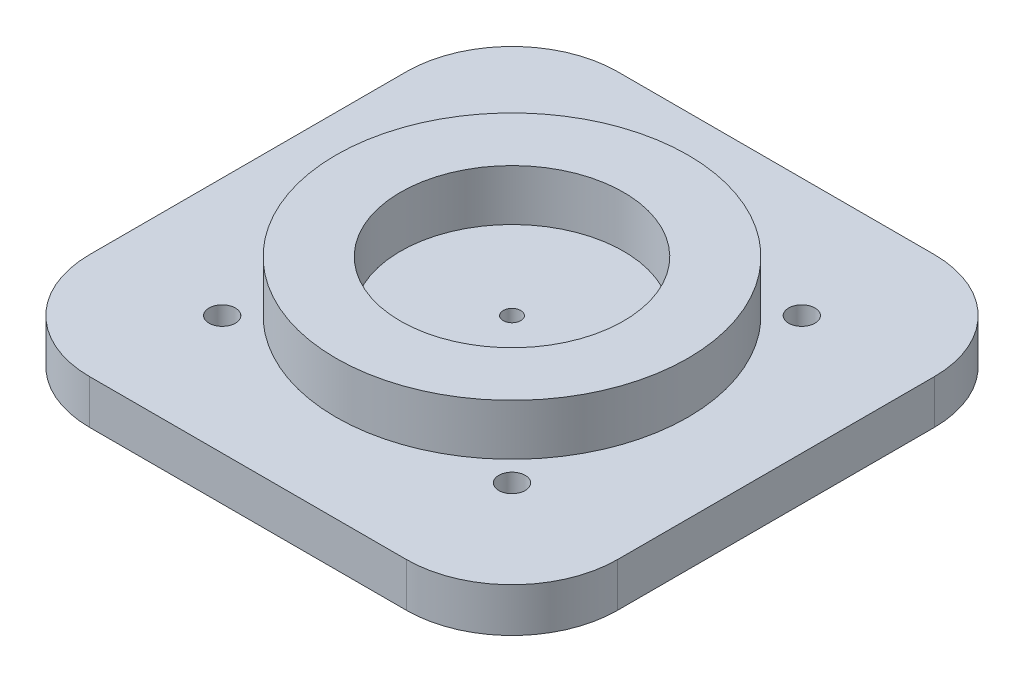
SolidWorks part; units mm, degrees
material "ABS PC"
ref_plane "Front Plane" through (0, 0, 0) normal (0, 0, 1) x (1, 0, 0)
ref_plane "Top Plane" through (0, 0, 0) normal (0, 1, 0) x (1, 0, 0)
ref_plane "Right Plane" through (0, 0, 0) normal (1, 0, 0) x (0, 0, -1)
sketch "Sketch1" plane through (0, 0, 0) normal (0, 1, 0) x (1, 0, 0)
  line L0 (0, 50.8) -> (4.4901, 46.3099)
  line L1 (0, 0) -> (50.8, 0)
  line L2 (0, 0) -> (0, 50.8)
  line L3 (0, 50.8) -> (50.8, 50.8)
  line L4 (50.8, 0) -> (50.8, 50.8)
  line L5 (0, 25.4) -> (50.8, 25.4) construction
  line L6 (25.4, 50.8) -> (25.4, 0) construction
  circle A0 centre (4.4901, 46.3099) radius 1.905
  circle A1 centre (4.4901, 4.4901) radius 1.905
  circle A2 centre (46.3099, 4.4901) radius 1.905
  circle A3 centre (46.3099, 46.3099) radius 1.905
  circle A28 centre (25.4, 25.4) radius 1.27
  dimension "D1" = 3.81
  dimension "D2" = 50.8
  dimension "D3" = 50.8
  dimension "D4" = 6.35
extrude "Boss-Extrude1" add sketch "Sketch1" along normal blind 6.35 contours A0 L2 L1 L4 L3 A1 A2 A3 region at (25.4, 0, -50.0816)
sketch "Sketch2" plane through (0, 0, 0) normal (0, 1, 0) x (1, 0, 0)
  line L0 (4.4901, 44.2975) -> (4.4901, 6.5025)
  line L1 (6.5025, 4.4901) -> (44.2975, 4.4901)
  line L2 (46.3099, 44.2975) -> (46.3099, 6.5025)
  line L3 (44.2975, 46.3099) -> (6.5025, 46.3099)
  circle A0 centre (4.4901, 46.3099) radius 1.905
  circle A1 centre (4.4901, 46.3099) radius 2.0124
  circle A2 centre (46.3099, 46.3099) radius 1.905
  circle A3 centre (46.3099, 46.3099) radius 2.0124
  circle A4 centre (46.3099, 4.4901) radius 1.905
  circle A5 centre (46.3099, 4.4901) radius 2.0124
  circle A6 centre (4.4901, 4.4901) radius 1.905
  circle A7 centre (4.4901, 4.4901) radius 2.0124
extrude "Cut-Extrude1" [suppressed] cut sketch "Sketch2" along normal blind 1.5875 from surface contours A7 L1 A5 L2 A3 L3 A1 L0 starting at face at (4.4901, 0, -44.4049)
sketch "Sketch3" plane through (0, 0, 0) normal (0, 1, 0) x (1, 0, 0)
  line L0 (3.2513, 44.2975) -> (3.2513, 6.5025)
  line L1 (6.5025, 3.2513) -> (44.2975, 3.2513)
  line L2 (47.5487, 44.2975) -> (47.5487, 6.5025)
  line L3 (44.2975, 47.5487) -> (6.5025, 47.5487)
  circle A0 centre (3.2513, 47.5487) radius 1.905
  circle A1 centre (3.2513, 47.5487) radius 3.2513
  circle A2 centre (47.5487, 47.5487) radius 1.905
  circle A3 centre (47.5487, 47.5487) radius 3.2513
  circle A4 centre (47.5487, 3.2513) radius 1.905
  circle A5 centre (47.5487, 3.2513) radius 3.2513
  circle A6 centre (3.2513, 3.2513) radius 1.905
  circle A7 centre (3.2513, 3.2513) radius 3.2513
extrude "Cut-Extrude2" [suppressed] cut sketch "Sketch3" against normal blind 1.5875 from surface contours A7 L1 A5 L2 A3 L3 A1 L0 starting at face at (4.4901, 6.35, -44.4049)
fillet "Fillet1" radius 2.54 4 edges at (50.8, 3.175, -50.8) (50.8, 3.175, 0) (0, 3.175, 0) (0, 3.175, -50.8)
sketch "Sketch4" plane through (0, 0, 0) normal (0, -1, 0) x (1, 0, 0)
  line L4 (10.2051, -4.4901) -> (40.5949, -4.4901)
  line L5 (46.3099, -10.2051) -> (46.3099, -40.5949)
  line L6 (40.5949, -46.3099) -> (10.2051, -46.3099)
  line L7 (4.4901, -40.5949) -> (4.4901, -10.2051)
  arc A4 (4.4901, -10.2051) -> (10.2051, -4.4901) centre (4.4901, -4.4901) ccw
  arc A5 (40.5949, -4.4901) -> (46.3099, -10.2051) centre (46.3099, -4.4901) ccw
  arc A6 (46.3099, -40.5949) -> (40.5949, -46.3099) centre (46.3099, -46.3099) ccw
  arc A7 (10.2051, -46.3099) -> (4.4901, -40.5949) centre (4.4901, -46.3099) ccw
  circle A8 centre (4.4901, -4.4901) radius 1.905
  dimension "D1" = 11.43
extrude "Cut-Extrude3" cut sketch "Sketch4" against normal blind 3.175
sketch "Sketch5" plane through (0, 6.35, 0) normal (0, 1, 0) x (1, 0, 0)
  line L8 (63.5, 2.54) -> (63.5, 48.26)
  line L9 (48.26, 63.5) -> (2.54, 63.5)
  line L10 (-12.7, 48.26) -> (-12.7, 2.54)
  line L11 (2.54, -12.7) -> (48.26, -12.7)
  line L12 (63.5, 2.54) -> (63.5, 48.26)
  line L13 (48.26, 63.5) -> (2.54, 63.5)
  line L14 (-12.7, 48.26) -> (-12.7, 2.54)
  line L15 (2.54, -12.7) -> (48.26, -12.7)
  line L16 (50.8, 2.54) -> (50.8, 48.26)
  line L17 (48.26, 50.8) -> (2.54, 50.8)
  line L18 (0, 48.26) -> (0, 2.54)
  line L19 (2.54, 0) -> (48.26, 0)
  line L20 (50.8, 2.54) -> (50.8, 48.26)
  line L21 (48.26, 50.8) -> (2.54, 50.8)
  line L22 (0, 48.26) -> (0, 2.54)
  line L23 (2.54, 0) -> (48.26, 0)
  arc A8 (63.5, 48.26) -> (48.26, 63.5) centre (48.26, 48.26) ccw
  arc A9 (2.54, 63.5) -> (-12.7, 48.26) centre (2.54, 48.26) ccw
  arc A10 (-12.7, 2.54) -> (2.54, -12.7) centre (2.54, 2.54) ccw
  arc A11 (48.26, -12.7) -> (63.5, 2.54) centre (48.26, 2.54) ccw
  arc A12 (63.5, 48.26) -> (48.26, 63.5) centre (48.26, 48.26) ccw
  arc A13 (2.54, 63.5) -> (-12.7, 48.26) centre (2.54, 48.26) ccw
  arc A14 (-12.7, 2.54) -> (2.54, -12.7) centre (2.54, 2.54) ccw
  arc A15 (48.26, -12.7) -> (63.5, 2.54) centre (48.26, 2.54) ccw
  arc A16 (50.8, 48.26) -> (48.26, 50.8) centre (48.26, 48.26) ccw
  arc A17 (2.54, 50.8) -> (0, 48.26) centre (2.54, 48.26) ccw
  arc A18 (0, 2.54) -> (2.54, 0) centre (2.54, 2.54) ccw
  arc A19 (48.26, 0) -> (50.8, 2.54) centre (48.26, 2.54) ccw
  arc A20 (50.8, 48.26) -> (48.26, 50.8) centre (48.26, 48.26) ccw
  arc A21 (2.54, 50.8) -> (0, 48.26) centre (2.54, 48.26) ccw
  arc A22 (0, 2.54) -> (2.54, 0) centre (2.54, 2.54) ccw
  arc A23 (48.26, 0) -> (50.8, 2.54) centre (48.26, 2.54) ccw
  dimension "D1" = 12.7
  dimension "D2" = 0
extrude "Boss-Extrude2" add sketch "Sketch5" against normal up to surface (6.35 mm away) up to face at (25.4, 0, -25.4)
sketch "Sketch6" plane through (0, 6.35, 0) normal (0, 1, 0) x (1, 0, 0)
  circle A0 centre (25.4, 25.4) radius 16.1
  circle A1 centre (25.4, 25.4) radius 25.4
  dimension "D1" = 50.8
  dimension "D2" = 32.2
extrude "Boss-Extrude3" add sketch "Sketch6" along normal blind 7.366
